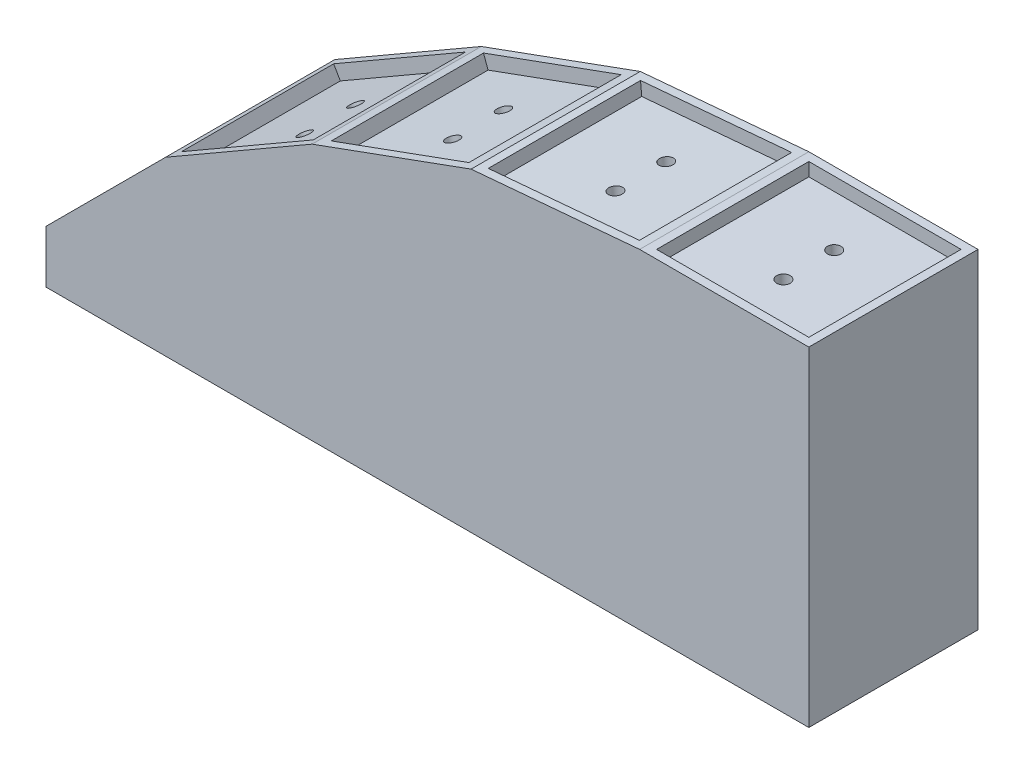
SolidWorks part; units mm, degrees
other "Markup1"
sketch "Sketch34" plane through (-281.715, -69.8831, -95.2498) normal (-0.9907, 0.0223, -0.134) x (-0.0947, 0.5934, 0.7993)
ref_plane "Front Plane" through (0, 0, 0) normal (0, 0, 1) x (1, 0, 0)
ref_plane "Top Plane" through (0, 0, 0) normal (0, 1, 0) x (1, 0, 0)
ref_plane "Right Plane" through (0, 0, 0) normal (1, 0, 0) x (0, 0, -1)
sketch "Sketch1" plane through (0, 0, 0) normal (0, 1, 0) x (1, 0, 0)
  line L1 (0, 0) -> (127, 0)
  line L2 (0, 0) -> (0, 127)
  line L3 (0, 127) -> (127, 127)
  line L4 (127, 0) -> (127, 127)
  line L5 (6.35, 120.65) -> (120.65, 120.65)
  line L6 (6.35, 120.65) -> (6.35, 6.35)
  line L7 (6.35, 6.35) -> (120.65, 6.35)
  line L8 (120.65, 120.65) -> (120.65, 6.35)
  dimension "D1" = 114.3
  dimension "D2" = 114.3
  dimension "D3" = 6.35
  dimension "D4" = 6.35
  dimension "D5" = 6.35
  dimension "D6" = 6.35
extrude "Boss-Extrude1" add sketch "Sketch1" along normal blind 10
ref_plane "Plane1" through (-0.8682, 9.924, 0) normal (-0.0872, 0.9962, 0) x (0, 0, 1)
sketch "Sketch18" plane through (-0.8682, 9.924, 0) normal (-0.0872, 0.9962, 0) x (0, 0, 1)
  line L1 (-127, 0.8716) -> (0, 0.8716)
  line L2 (-127, 0.8716) -> (-127, -126.1284)
  line L3 (-127, -126.1284) -> (0, -126.1284)
  line L4 (0, 0.8716) -> (0, -126.1284)
  dimension "D1" = 127
  dimension "D2" = 127
extrude "Boss-Extrude17" add sketch "Sketch18" against normal blind 10
ref_plane "Plane8" through (-14.4561, 39.7179, 0) normal (-0.342, 0.9397, 0) x (0, 0, 1)
sketch "Sketch20" plane through (-14.4561, 39.7179, 0) normal (-0.342, 0.9397, 0) x (0, 0, 1)
  line L1 (-127, -119.2524) -> (0, -119.2524)
  line L2 (-127, -119.2524) -> (-127, -246.2524)
  line L3 (-127, -246.2524) -> (0, -246.2524)
  line L4 (0, -119.2524) -> (0, -246.2524)
  dimension "D1" = 127
  dimension "D2" = 127
extrude "Boss-Extrude19" add sketch "Sketch20" against normal blind 10
sketch "Sketch21" plane through (-0.8682, 9.924, 0) normal (-0.0872, 0.9962, 0) x (0.9962, 0.0872, 0)
  line L0 (121.0624, 120.65) -> (7.1974, 120.65) construction
  line L1 (-119.561, 120.65) -> (-5.6959, 120.65)
  line L2 (-119.561, 120.65) -> (-119.561, 6.35)
  line L3 (-119.561, 6.35) -> (-5.6959, 6.35)
  line L4 (-5.6959, 120.65) -> (-5.6959, 6.35)
  line L5 (7.1974, 120.65) -> (7.1974, 6.35) construction
  line L6 (0.8716, 127) -> (-126.1284, 127) construction
  line L7 (-126.1284, 127) -> (-126.1284, 0) construction
  point P10 (-62.6284, 127)
  point P11 (-62.6284, 120.65)
  point P14 (-126.1284, 63.5)
  point P15 (-119.561, 63.5)
extrude "Cut-Extrude1" cut sketch "Sketch21" against normal blind 10
sketch "Sketch22" plane through (-14.4561, 39.7179, 0) normal (-0.342, 0.9397, 0) x (0.9397, 0.342, 0)
  line L0 (-246.2524, 127) -> (-246.2524, 0) construction
  line L1 (-237.745, 120.65) -> (-127.7598, 120.65)
  line L2 (-237.745, 120.65) -> (-237.745, 6.35)
  line L3 (-237.745, 6.35) -> (-127.7598, 6.35)
  line L4 (-127.7598, 120.65) -> (-127.7598, 6.35)
  line L5 (-119.2524, 127) -> (-246.2524, 127) construction
  line L6 (-2.9235, 120.65) -> (-112.9087, 120.65) construction
  line L7 (-112.9087, 120.65) -> (-112.9087, 6.35) construction
  point P6 (-246.2524, 63.5)
  point P7 (-237.745, 63.5)
  point P10 (-182.7524, 127)
  point P11 (-182.7524, 120.65)
extrude "Cut-Extrude2" cut sketch "Sketch22" against normal blind 10
sketch "Sketch23" plane through (0, 0, 0) normal (0, -1, 0) x (1, 0, 0)
  line L1 (0, 0) -> (127, 0)
  line L2 (0, 0) -> (0, -127)
  line L3 (0, -127) -> (127, -127)
  line L4 (127, 0) -> (127, -127)
extrude "Boss-Extrude21" add sketch "Sketch23" along normal blind 10
sketch "Sketch24" plane through (0.0033, -0.0379, 0) normal (0.0872, -0.9962, 0) x (0.9962, 0.0872, 0)
  line L0 (-124.8119, 0) -> (-0.0033, 0) construction
  line L1 (-124.8119, 0) -> (2.1881, 0)
  line L2 (-124.8119, 0) -> (-124.8119, -127)
  line L3 (-124.8119, -127) -> (2.1881, -127)
  line L4 (2.1881, 0) -> (2.1881, -127)
  line L5 (-0.0033, -127) -> (-124.8119, -127) construction
  dimension "D1" = 127
extrude "Boss-Extrude24" add sketch "Sketch24" along normal blind 10
sketch "Sketch25" plane through (-11.0359, 30.321, 0) normal (0.342, -0.9397, 0) x (0.9397, 0.342, 0)
  line L0 (-246.2524, -127) -> (-246.2524, 0) construction
  line L1 (-246.2524, 0) -> (-119.2524, 0)
  line L2 (-246.2524, 0) -> (-246.2524, -127)
  line L3 (-246.2524, -127) -> (-119.2524, -127)
  line L4 (-119.2524, 0) -> (-119.2524, -127)
  dimension "D1" = 127
  dimension "D2" = 127
extrude "Boss-Extrude25" add sketch "Sketch25" along normal blind 10
ref_plane "Plane9" through (-42.193, 73.0805, 0) normal (-0.5, 0.866, 0) x (0, 0, 1)
sketch "Sketch26" plane through (-42.193, 73.0805, 0) normal (-0.5, 0.866, 0) x (0, 0, 1)
  line L1 (-127, -235.1717) -> (0, -235.1717)
  line L2 (-127, -235.1717) -> (-127, -362.1717)
  line L3 (-127, -362.1717) -> (0, -362.1717)
  line L4 (0, -235.1717) -> (0, -362.1717)
  dimension "D1" = 127
  dimension "D2" = 127
extrude "Boss-Extrude26" add sketch "Sketch26" against normal blind 10
sketch "Sketch27" plane through (-42.193, 73.0805, 0) normal (-0.5, 0.866, 0) x (0.866, 0.5, 0)
  line L0 (-235.1717, 127) -> (-362.1717, 127) construction
  line L1 (-355.8217, 120.65) -> (-241.5217, 120.65)
  line L2 (-355.8217, 120.65) -> (-355.8217, 6.35)
  line L3 (-355.8217, 6.35) -> (-241.5217, 6.35)
  line L4 (-241.5217, 120.65) -> (-241.5217, 6.35)
  line L5 (-362.1717, 127) -> (-362.1717, 0) construction
  point P6 (-298.6717, 127)
  point P7 (-298.6717, 120.65)
  point P10 (-362.1717, 63.5)
  point P11 (-355.8217, 63.5)
  dimension "D1" = 114.3
  dimension "D2" = 114.3
extrude "Cut-Extrude3" cut sketch "Sketch27" against normal blind 10
sketch "Sketch28" plane through (-37.193, 64.4202, 0) normal (0.5, -0.866, 0) x (0.866, 0.5, 0)
  line L1 (-362.1717, 0) -> (-235.1717, 0)
  line L2 (-362.1717, 0) -> (-362.1717, -127)
  line L3 (-362.1717, -127) -> (-235.1717, -127)
  line L4 (-235.1717, 0) -> (-235.1717, -127)
  dimension "D1" = 127
  dimension "D2" = 127
extrude "Boss-Extrude27" add sketch "Sketch28" along normal blind 10
ref_plane "Plane10" through (-123.9188, 123.9188, 0) normal (-0.7071, 0.7071, 0) x (0, 0, 1)
sketch "Sketch29" plane through (-123.9188, 123.9188, 0) normal (-0.7071, 0.7071, 0) x (0, 0, 1)
  line L1 (-127, -327.9902) -> (0, -327.9902)
  line L2 (-127, -327.9902) -> (-127, -454.9902)
  line L3 (-127, -454.9902) -> (0, -454.9902)
  line L4 (0, -327.9902) -> (0, -454.9902)
  dimension "D1" = 127
  dimension "D2" = 127
extrude "Boss-Extrude28" add sketch "Sketch29" against normal blind 10
sketch "Sketch30" plane through (-123.9188, 123.9188, 0) normal (-0.7071, 0.7071, 0) x (0, 0, 1)
  line L0 (-127, -454.9902) -> (0, -454.9902) construction
  line L1 (-120.65, -334.3402) -> (-6.35, -334.3402)
  line L2 (-120.65, -334.3402) -> (-120.65, -448.6402)
  line L3 (-120.65, -448.6402) -> (-6.35, -448.6402)
  line L4 (-6.35, -334.3402) -> (-6.35, -448.6402)
  line L5 (-127, -327.9902) -> (-127, -454.9902) construction
  point P6 (-63.5, -454.9902)
  point P7 (-63.5, -448.6402)
  point P10 (-127, -391.4902)
  point P11 (-120.65, -391.4902)
  dimension "D1" = 114.3
  dimension "D2" = 114.3
extrude "Cut-Extrude4" cut sketch "Sketch30" against normal blind 10
sketch "Sketch31" plane through (-116.8477, 116.8477, 0) normal (0.7071, -0.7071, 0) x (0, 0, -1)
  line L1 (0, -454.9902) -> (127, -454.9902)
  line L2 (0, -454.9902) -> (0, -327.9902)
  line L3 (0, -327.9902) -> (127, -327.9902)
  line L4 (127, -454.9902) -> (127, -327.9902)
  dimension "D1" = 127
  dimension "D2" = 127
extrude "Boss-Extrude29" add sketch "Sketch31" along normal blind 10
sketch "Sketch32" plane through (0, 0, 0) normal (0, 0, 1) x (1, 0, 0)
  line L1 (127, -237.35) -> (127, -10)
  line L2 (127, -10) -> (0.8732, -10)
  line L3 (0.8732, -10) -> (-122.1506, -20.7632)
  line L4 (-122.1506, -20.7632) -> (-237.373, -62.7007)
  line L5 (-237.373, -62.7007) -> (-343.5626, -124.0093)
  line L6 (-343.5626, -124.0093) -> (-431.5033, -211.95)
  line L11 (127, -237.35) -> (-445.6455, -237.35)
  line L12 (-445.6455, -237.35) -> (-445.6455, -197.8079)
  line L13 (-445.6455, -197.8079) -> (-431.5033, -211.95)
  dimension "D1" = 25.4
extrude "Boss-Extrude30" add sketch "Sketch32" against normal up to surface (127 mm away) up to face at (-171.1316, -64.2342, -127)
sketch "Sketch33" plane through (0, 0, -127) normal (0, 0, -1) x (-1, 0, 0)
  line L0 (-127, 10) -> (-127, -237.35) construction
  line L1 (-127, 10) -> (0, 10) construction
  line L2 (0, 10) -> (126.5167, -1.0688) construction
  line L3 (126.5167, -1.0688) -> (245.8577, -44.5053) construction
  line L4 (245.8577, -44.5053) -> (355.8429, -108.0053) construction
  line L5 (355.8429, -108.0053) -> (445.6455, -197.8079) construction
  text T0 "0"
  text T1 "5"
  text T2 "15\r\n"
  text T3 "30\r\n"
  text T4 "45\r\n"
  dimension "D1" = 63.5
  dimension "D2" = 12.7
  dimension "D3" = 12.7
  dimension "D4" = 190.5
  dimension "D5" = 12.7
  dimension "D6" = 317.5
  dimension "D7" = 12.7
  dimension "D8" = 419.1
  dimension "D9" = 12.7
  dimension "D10" = 520.7
extrude "Cut-Extrude5" cut sketch "Sketch33" against normal blind 2.54
scale "Scale5" scale about centroid uniform scaling yes scale factor 0.5
sketch "Sketch35" plane through (0, -66.7667, 0) normal (0, 1, 0) x (1, 0, 0)
  line L0 (4.7218, 34.9249) -> (4.7218, 92.0749) construction
  line L1 (4.7218, 92.0749) -> (-52.4282, 92.0749) construction
  line L2 (-52.4282, 34.9249) -> (4.7218, 34.9249) construction
  circle A0 centre (-23.8532, 73.0249) radius 2.5273
  circle A1 centre (-23.8532, 53.9749) radius 2.5273
  point P4 (0, 0)
  dimension "D1" = 5.0546
  dimension "D2" = 28.575
  dimension "D3" = 19.05
  dimension "D4" = 19.05
extrude "Cut-Extrude6" cut sketch "Sketch35" against normal blind 9
sketch "Sketch36" plane through (5.3762, -61.4507, 0) normal (-0.0872, 0.9962, 0) x (0.9962, 0.0872, 0)
  line L0 (-64.0587, 92.0749) -> (-120.9912, 92.0749) construction
  line L1 (-120.9912, 34.9249) -> (-64.0587, 34.9249) construction
  line L2 (-64.0587, 34.9249) -> (-64.0587, 92.0749) construction
  circle A0 centre (-92.6337, 73.0249) radius 2.5273
  circle A1 centre (-92.6337, 53.9749) radius 2.5273
  point P4 (0, 0)
  dimension "D1" = 5.0546
  dimension "D2" = 19.05
  dimension "D3" = 19.05
  dimension "D4" = 28.575
extrude "Cut-Extrude7" cut sketch "Sketch36" against normal blind 9
sketch "Sketch37" plane through (9.4361, -25.9254, 0) normal (-0.342, 0.9397, 0) x (0.9397, 0.342, 0)
  line L0 (-138.9654, 92.0749) -> (-193.958, 92.0749) construction
  line L1 (-193.958, 34.9249) -> (-138.9654, 34.9249) construction
  line L2 (-138.9654, 34.9249) -> (-138.9654, 92.0749) construction
  circle A0 centre (-167.5404, 73.0249) radius 2.5273
  circle A1 centre (-167.5404, 53.9749) radius 2.5273
  point P4 (0, 0)
  dimension "D1" = 5.0546
  dimension "D2" = 19.05
  dimension "D3" = 19.05
  dimension "D4" = 28.575
extrude "Cut-Extrude8" cut sketch "Sketch37" against normal blind 9
sketch "Sketch38" plane through (-3.5865, 6.212, 0) normal (-0.5, 0.866, 0) x (0.866, 0.5, 0)
  line L1 (-202.298, 92.0749) -> (-259.448, 92.0749) construction
  line L2 (-259.448, 34.9249) -> (-202.298, 34.9249) construction
  line L3 (-202.298, 34.9249) -> (-202.298, 92.0749) construction
  circle A0 centre (-230.873, 73.0249) radius 2.5273
  circle A1 centre (-230.873, 53.9749) radius 2.5273
  point P6 (0, 0)
  dimension "D1" = 5.0546
  dimension "D2" = 19.05
  dimension "D3" = 19.05
  dimension "D4" = 28.575
extrude "Cut-Extrude9" cut sketch "Sketch38" against normal blind 9
sketch "Sketch39" plane through (-52.8421, 52.8421, 0) normal (-0.7071, 0.7071, 0) x (0, 0, 1)
  line L0 (-92.0749, -253.6987) -> (-92.0749, -310.8487) construction
  line L1 (-34.9249, -310.8487) -> (-34.9249, -253.6987) construction
  line L2 (-34.9249, -253.6987) -> (-92.0749, -253.6987) construction
  circle A0 centre (-73.0249, -282.2737) radius 2.5273
  circle A1 centre (-53.9749, -282.2737) radius 2.5273
  point P4 (0, 0)
  point P7 (-54.2257, -288.0653)
  dimension "D1" = 5.0546
  dimension "D2" = 19.05
  dimension "D3" = 19.05
  dimension "D4" = 28.575
extrude "Cut-Extrude10" cut sketch "Sketch39" against normal blind 9
